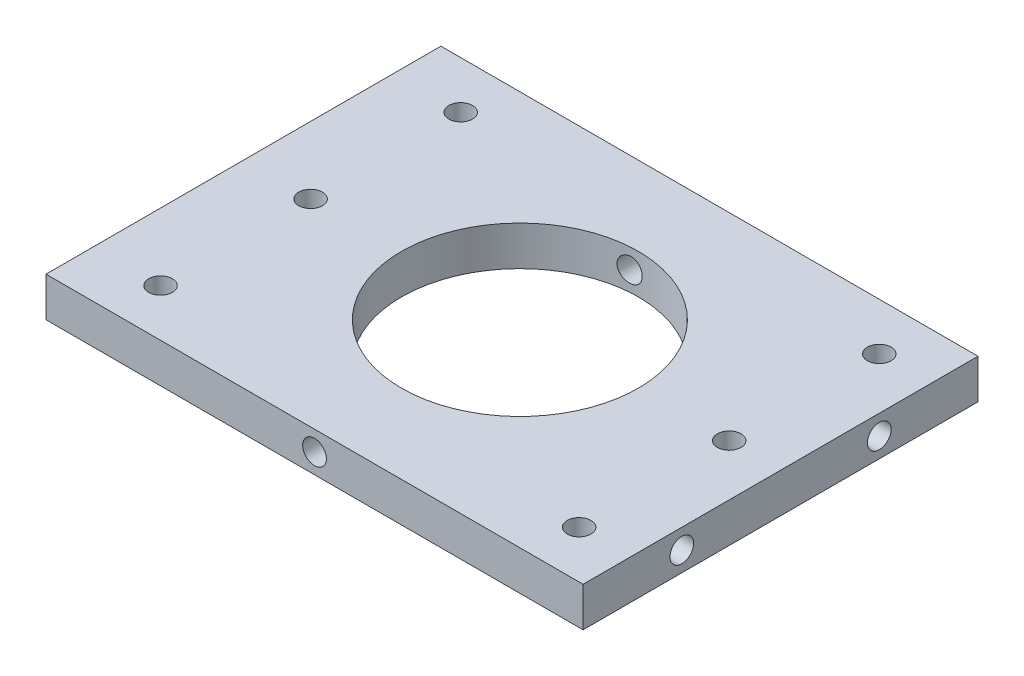
SolidWorks part; units mm, degrees
ref_plane "Plan de face" through (0, 0, 0) normal (0, 0, 1) x (1, 0, 0)
ref_plane "Plan de dessus" through (0, 0, 0) normal (0, 1, 0) x (1, 0, 0)
ref_plane "Plan de droite" through (0, 0, 0) normal (1, 0, 0) x (0, 0, -1)
sketch "Esquisse1" plane through (0, 0, 0) normal (0, 0, 1) x (1, 0, 0)
  line L0 (-15.5, -47.5) -> (52.5, -47.5) construction
  line L5 (-15.5, -45) -> (52.5, -45)
  line L6 (-15.5, -45) -> (-15.5, -50)
  line L7 (-15.5, -50) -> (52.5, -50)
  line L8 (52.5, -45) -> (52.5, -50)
  line L9 (18.5, -45) -> (18.5, -50) construction
  dimension "D1" = 5
  dimension "D2" = 68
extrude "Boss.-Extru.1" add sketch "Esquisse1" along normal blind 50 contours L5 | L7 L8 L5 L6
sketch "Esquisse2" plane through (0, -45, 0) normal (0, 1, 0) x (-1, 0, 0)
  line L0 (15.5, 50) -> (-52.5, 50) construction
  line L1 (15.5, 0) -> (-52.5, 0) construction
  line L7 (-52.5, 50) -> (-52.5, 0) construction
  circle A0 centre (-19.5, 25) radius 15
  circle A1 centre (-46, 44) radius 1.5
  circle A2 centre (-46, 6) radius 1.5
  circle A3 centre (7, 44) radius 1.5
  circle A4 centre (7, 6) radius 1.5
  circle A6 centre (7, 25) radius 1.5
  circle A7 centre (-46, 25) radius 1.5
  dimension "D6" = 6
  dimension "D2" = 53
  dimension "D3" = 53
  dimension "D4" = 26.5
  dimension "D5" = 26.5
  dimension "D7" = 6
  dimension "D8" = 6
  dimension "D9" = 6
  dimension "D10" = 33
  dimension "D11" = 25
  dimension "D12" = 25
  dimension "D13" = 25
extrude "Enlèv. mat.-Extru.1" cut sketch "Esquisse2" against normal through all
sketch "Esquisse3" plane through (-15.5, 0, 0) normal (-1, 0, 0) x (0, 0, 1)
  line L0 (50, -50) -> (0, -50) construction
  line L1 (0, -45) -> (0, -50) construction
  line L2 (50, -45) -> (50, -50) construction
  circle A0 centre (12.5, -47.5) radius 1.5
  circle A1 centre (37.5, -47.5) radius 1.5
  dimension "D1" = 2.5
  dimension "D2" = 2.5
  dimension "D3" = 12.5
  dimension "D4" = 12.5
extrude "Enlèv. mat.-Extru.2" cut sketch "Esquisse3" against normal blind 10
sketch "Esquisse4" plane through (52.5, 0, 0) normal (1, 0, 0) x (0, 0, -1)
  line L0 (-50, -50) -> (0, -50) construction
  line L1 (-50, -45) -> (-50, -50) construction
  line L2 (0, -45) -> (0, -50) construction
  circle A0 centre (-37.5, -47.5) radius 1.5
  circle A1 centre (-12.5, -47.5) radius 1.5
  dimension "D1" = 2.5
  dimension "D2" = 2.5
  dimension "D3" = 12.5
  dimension "D4" = 12.5
extrude "Enlèv. mat.-Extru.3" cut sketch "Esquisse4" against normal blind 10
sketch "Esquisse5" plane through (0, 0, 50) normal (0, 0, 1) x (1, 0, 0)
  line L0 (-15.5, -45) -> (52.5, -45) construction
  line L1 (-15.5, -45) -> (-15.5, -50) construction
  circle A0 centre (18.5, -47.5) radius 1.5
  dimension "D1" = 2.5
  dimension "D2" = 34
extrude "Enlèv. mat.-Extru.4" cut sketch "Esquisse5" against normal through all
